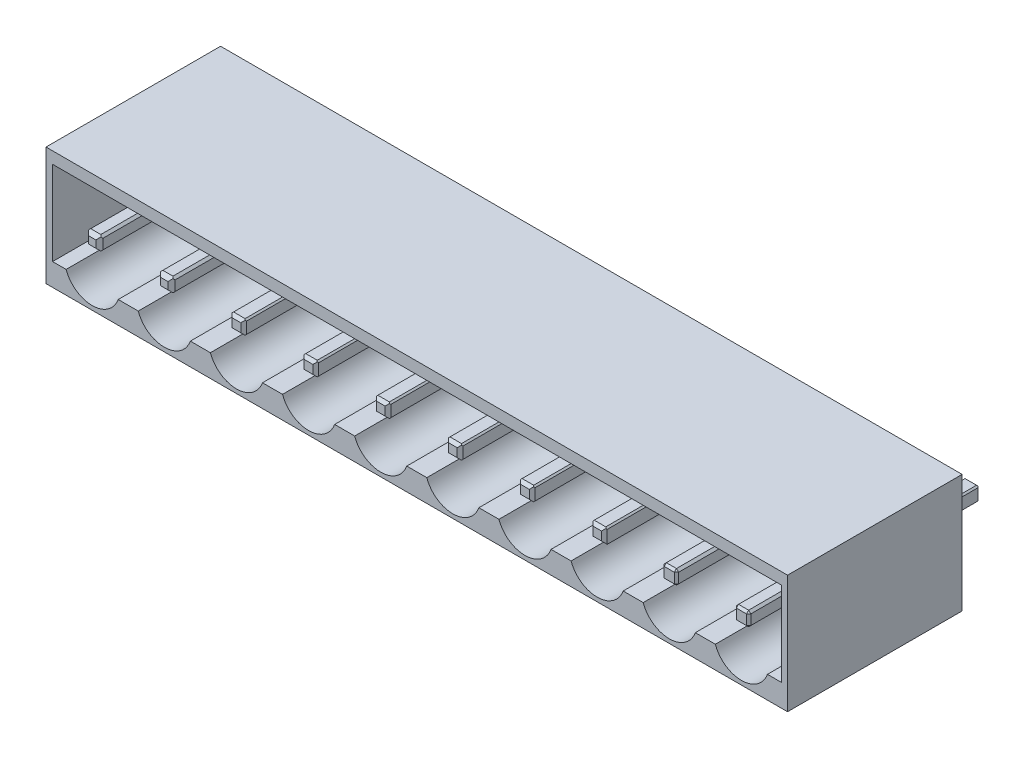
SolidWorks part; units mm, degrees
ref_plane "Спереди" through (0, 0, 0) normal (0, 0, 1) x (1, 0, 0)
ref_plane "Сверху" through (0, 0, 0) normal (0, 1, 0) x (1, 0, 0)
ref_plane "Справа" through (0, 0, 0) normal (1, 0, 0) x (0, 0, -1)
sketch "Эскиз1" plane through (0, 0, 0) normal (0, 0, 1) x (1, 0, 0)
  line L1 (-25.7, 4.1) -> (25.7, 4.1)
  line L2 (-25.7, 4.1) -> (-25.7, -4.1)
  line L3 (-25.7, -4.1) -> (25.7, -4.1)
  line L4 (25.7, 4.1) -> (25.7, -4.1)
  line L5 (-25.7, 4.1) -> (25.7, -4.1) construction
  line L6 (-25.7, -4.1) -> (25.7, 4.1) construction
  point P0 (0, 0)
  dimension "D1" = 8.2
  dimension "D2" = 51.4
extrude "Бобышка-Вытянуть1" add sketch "Эскиз1" along normal blind 12.1
sketch "Эскиз4" plane through (0, 0, 12.1) normal (0, 0, 1) x (1, 0, 0)
  circle A0 centre (-22.5, 0) radius 1.25
  circle A1 centre (-17.5, 0) radius 1.25
  circle A2 centre (-12.5, 0) radius 1.25
  circle A3 centre (-7.5, 0) radius 1.25
  circle A4 centre (-2.5, 0) radius 1.25
  circle A5 centre (2.5, 0) radius 1.25
  circle A6 centre (7.5, 0) radius 1.25
  circle A7 centre (12.5, 0) radius 1.25
  circle A8 centre (17.5, 0) radius 1.25
  circle A9 centre (22.5, 0) radius 1.25
  dimension "D1" = 2.5
  dimension "D2" = 3.2
  dimension "D5" = 2
  dimension "D3" = 2
  dimension "D4" = 2
  dimension "D6" = 3
  dimension "D7" = 2
  dimension "D8" = 2
extrude "Вырез-Вытянуть3" cut sketch "Эскиз4" against normal blind 8
sketch "Эскиз5" plane through (0, 0, 12.1) normal (0, 0, 1) x (1, 0, 0)
  line L0 (-25.2456, 0) -> (-25.2456, 3.2929)
  line L1 (-25.2456, 3.2929) -> (-14.7215, 3.2929)
  line L4 (-25.2456, -2.549) -> (-25.2456, 0)
  line L5 (-15.6942, -2.549) -> (-14.3058, -2.549)
  line L6 (-24.3058, -2.549) -> (-25.2456, -2.549)
  line L7 (-20.6942, -2.549) -> (-19.3058, -2.549)
  line L11 (-14.7215, 3.2929) -> (-9.7215, 3.2929)
  line L13 (-15.6942, -2.549) -> (-14.3058, -2.549) [skipped]
  line L15 (-10.6942, -2.549) -> (-9.3058, -2.549)
  line L16 (-9.7215, 3.2929) -> (-4.7215, 3.2929)
  line L17 (-0.6942, -2.549) -> (0.6942, -2.549)
  line L20 (-5.6942, -2.549) -> (-4.3058, -2.549)
  line L21 (-4.7215, 3.2929) -> (5.2785, 3.2929)
  line L22 (9.3058, -2.549) -> (10.6942, -2.549)
  line L25 (5.2785, 3.2929) -> (15.2785, 3.2929)
  line L26 (4.3058, -2.549) -> (5.6942, -2.549)
  line L27 (19.3058, -2.549) -> (20.6942, -2.549)
  line L28 (24.3058, -2.549) -> (25.2785, -2.549)
  line L29 (25.2785, 3.2929) -> (25.2785, -2.549)
  line L30 (15.2785, 3.2929) -> (25.2785, 3.2929)
  line L31 (14.3058, -2.549) -> (15.6942, -2.549)
  arc A1 (-14.3058, -2.549) -> (-10.6942, -2.549) centre (-12.5, -1.9) ccw
  arc A2 (-9.3058, -2.549) -> (-5.6942, -2.549) centre (-7.5, -1.9) ccw
  arc A4 (-4.3058, -2.549) -> (-0.6942, -2.549) centre (-2.5, -1.9) ccw
  arc A5 (-24.3058, -2.549) -> (-20.6942, -2.549) centre (-22.5, -1.9) ccw
  arc A6 (-19.3058, -2.549) -> (-15.6942, -2.549) centre (-17.5, -1.9) ccw
  arc A7 (0.6942, -2.549) -> (4.3058, -2.549) centre (2.5, -1.9) ccw
  arc A8 (5.6942, -2.549) -> (9.3058, -2.549) centre (7.5, -1.9) ccw
  arc A9 (10.6942, -2.549) -> (14.3058, -2.549) centre (12.5, -1.9) ccw
  arc A10 (15.6942, -2.549) -> (19.3058, -2.549) centre (17.5, -1.9) ccw
  arc A11 (20.6942, -2.549) -> (24.3058, -2.549) centre (22.5, -1.9) ccw
  dimension "D1" = 3.2
  dimension "D2" = 2.2
  dimension "D3" = 2
  dimension "D4" = 2
  dimension "D5" = 2
  dimension "D6" = 2
  dimension "D7" = 2
  dimension "D8" = 2
extrude "Вырез-Вытянуть4" cut sketch "Эскиз5" against normal blind 7.8
sketch "Эскиз7" plane through (0, 0, 4.1) normal (0, 0, 1) x (1, 0, 0)
  line L0 (-18, 0.5) -> (-17, 0.5)
  line L1 (-23, 0.5) -> (-22, 0.5)
  line L2 (-23, 0.5) -> (-23, -0.5)
  line L3 (-23, -0.5) -> (-22, -0.5)
  line L4 (-22, 0.5) -> (-22, -0.5)
  line L5 (-23, 0.5) -> (-22, -0.5) construction
  line L6 (-23, -0.5) -> (-22, 0.5) construction
  line L7 (-18, 0.5) -> (-18, -0.5)
  line L8 (-18, -0.5) -> (-17, -0.5)
  line L9 (-17, 0.5) -> (-17, -0.5)
  line L10 (-18, 0.5) -> (-17, -0.5) construction
  line L11 (-18, -0.5) -> (-17, 0.5) construction
  line L12 (-13, 0.5) -> (-12, 0.5)
  line L13 (-13, 0.5) -> (-13, -0.5)
  line L14 (-13, -0.5) -> (-12, -0.5)
  line L15 (-12, 0.5) -> (-12, -0.5)
  line L16 (-13, 0.5) -> (-12, -0.5) construction
  line L17 (-13, -0.5) -> (-12, 0.5) construction
  line L18 (-8, 0.5) -> (-7, 0.5)
  line L19 (-8, 0.5) -> (-8, -0.5)
  line L20 (-8, -0.5) -> (-7, -0.5)
  line L21 (-7, 0.5) -> (-7, -0.5)
  line L22 (-8, 0.5) -> (-7, -0.5) construction
  line L23 (-8, -0.5) -> (-7, 0.5) construction
  line L24 (-3, 0.5) -> (-2, 0.5)
  line L25 (-3, 0.5) -> (-3, -0.5)
  line L26 (-3, -0.5) -> (-2, -0.5)
  line L27 (-2, 0.5) -> (-2, -0.5)
  line L28 (2, 0.5) -> (3, 0.5)
  line L29 (2, 0.5) -> (2, -0.5)
  line L30 (2, -0.5) -> (3, -0.5)
  line L31 (3, 0.5) -> (3, -0.5)
  line L32 (-3, 0.5) -> (-2, -0.5) construction
  line L33 (-3, -0.5) -> (-2, 0.5) construction
  line L34 (2, 0.5) -> (3, -0.5) construction
  line L35 (2, -0.5) -> (3, 0.5) construction
  line L36 (7, 0.5) -> (8, 0.5)
  line L37 (7, 0.5) -> (7, -0.5)
  line L38 (7, -0.5) -> (8, -0.5)
  line L39 (8, 0.5) -> (8, -0.5)
  line L40 (12, 0.5) -> (13, 0.5)
  line L41 (12, 0.5) -> (12, -0.5)
  line L42 (12, -0.5) -> (13, -0.5)
  line L43 (13, 0.5) -> (13, -0.5)
  line L44 (7, 0.5) -> (8, -0.5) construction
  line L45 (7, -0.5) -> (8, 0.5) construction
  line L46 (12, 0.5) -> (13, -0.5) construction
  line L47 (12, -0.5) -> (13, 0.5) construction
  line L48 (17, 0.5) -> (18, 0.5)
  line L49 (17, 0.5) -> (17, -0.5)
  line L50 (17, -0.5) -> (18, -0.5)
  line L51 (18, 0.5) -> (18, -0.5)
  line L52 (22, 0.5) -> (23, 0.5)
  line L53 (22, 0.5) -> (22, -0.5)
  line L54 (22, -0.5) -> (23, -0.5)
  line L55 (23, 0.5) -> (23, -0.5)
  line L56 (17, 0.5) -> (18, -0.5) construction
  line L57 (17, -0.5) -> (18, 0.5) construction
  line L58 (22, 0.5) -> (23, -0.5) construction
  line L59 (22, -0.5) -> (23, 0.5) construction
  point P0 (-22.5, 0)
  point P7 (-17.5, 0)
  point P12 (-12.5, 0)
  point P17 (-7.5, 0)
  point P23 (-2.5, 0)
  point P28 (2.5, 0)
  point P33 (7.5, 0)
  point P38 (12.5, 0)
  point P43 (17.5, 0)
  point P48 (22.5, 0)
  dimension "D1" = 1
  dimension "D2" = 1
  dimension "D3" = 2
  dimension "D4" = 2
  dimension "D5" = 2
  dimension "D6" = 2
  dimension "D7" = 2
  dimension "D8" = 2
extrude "Бобышка-Вытянуть2" add sketch "Эскиз7" along normal blind 8
chamfer "Фаска1" distance 0.15 angle 45 24 edges at (-18, -0.5, 8.1) (-18, 0.5, 8.1) (-17, 0.5, 8.1) (-17, -0.5, 8.1) (-22, -0.5, 8.1) (-22, 0.5, 8.1) (-23, -0.5, 8.1) (-23, 0.5, 8.1) (23, 0, 12.1) (23, -0.5, 8.1) (22.5, -0.5, 12.1) (22, -0.5, 8.1) (22, 0, 12.1) (22, 0.5, 8.1) (22.5, 0.5, 12.1) (23, 0.5, 8.1) (18, 0, 12.1) (18, -0.5, 8.1) (17.5, -0.5, 12.1) (17, -0.5, 8.1) (17, 0, 12.1) (17, 0.5, 8.1) (17.5, 0.5, 12.1) (18, 0.5, 8.1)
chamfer "Фаска2" distance 0.25 angle 45 8 edges at (-18, 0, 12.1) (-17.5, 0.5, 12.1) (-17, 0, 12.1) (-17.5, -0.5, 12.1) (-22, 0, 12.1) (-22.5, -0.5, 12.1) (-23, 0, 12.1) (-22.5, 0.5, 12.1)
sketch "Эскиз8" plane through (0, -4.1, 0) normal (0, 0, 1) x (-1, 0, 0)
  line L0 (18, -4.25) -> (17, -4.25)
  line L1 (23, -4.25) -> (22, -4.25)
  line L2 (23, -4.25) -> (23, -3.25)
  line L3 (23, -3.25) -> (22, -3.25)
  line L4 (22, -4.25) -> (22, -3.25)
  line L5 (23, -4.25) -> (22, -3.25) construction
  line L6 (23, -3.25) -> (22, -4.25) construction
  line L7 (18, -4.25) -> (18, -3.25)
  line L8 (18, -3.25) -> (17, -3.25)
  line L9 (17, -4.25) -> (17, -3.25)
  line L10 (18, -4.25) -> (17, -3.25) construction
  line L11 (18, -3.25) -> (17, -4.25) construction
  line L12 (13, -4.25) -> (12, -4.25)
  line L13 (13, -4.25) -> (13, -3.25)
  line L14 (13, -3.25) -> (12, -3.25)
  line L15 (12, -4.25) -> (12, -3.25)
  line L16 (13, -4.25) -> (12, -3.25) construction
  line L17 (13, -3.25) -> (12, -4.25) construction
  line L18 (8, -4.25) -> (7, -4.25)
  line L19 (8, -4.25) -> (8, -3.25)
  line L20 (8, -3.25) -> (7, -3.25)
  line L21 (7, -4.25) -> (7, -3.25)
  line L22 (8, -4.25) -> (7, -3.25) construction
  line L23 (8, -3.25) -> (7, -4.25) construction
  line L24 (3, -4.25) -> (2, -4.25)
  line L25 (3, -4.25) -> (3, -3.25)
  line L26 (3, -3.25) -> (2, -3.25)
  line L27 (2, -4.25) -> (2, -3.25)
  line L28 (-2, -4.25) -> (-3, -4.25)
  line L29 (-2, -4.25) -> (-2, -3.25)
  line L30 (-2, -3.25) -> (-3, -3.25)
  line L31 (-3, -4.25) -> (-3, -3.25)
  line L32 (3, -4.25) -> (2, -3.25) construction
  line L33 (3, -3.25) -> (2, -4.25) construction
  line L34 (-2, -4.25) -> (-3, -3.25) construction
  line L35 (-2, -3.25) -> (-3, -4.25) construction
  line L36 (-7, -4.25) -> (-8, -4.25)
  line L37 (-7, -4.25) -> (-7, -3.25)
  line L38 (-7, -3.25) -> (-8, -3.25)
  line L39 (-8, -4.25) -> (-8, -3.25)
  line L40 (-12, -4.25) -> (-13, -4.25)
  line L41 (-12, -4.25) -> (-12, -3.25)
  line L42 (-12, -3.25) -> (-13, -3.25)
  line L43 (-13, -4.25) -> (-13, -3.25)
  line L44 (-7, -4.25) -> (-8, -3.25) construction
  line L45 (-7, -3.25) -> (-8, -4.25) construction
  line L46 (-12, -4.25) -> (-13, -3.25) construction
  line L47 (-12, -3.25) -> (-13, -4.25) construction
  line L48 (-17, -4.25) -> (-18, -4.25)
  line L49 (-17, -4.25) -> (-17, -3.25)
  line L50 (-17, -3.25) -> (-18, -3.25)
  line L51 (-18, -4.25) -> (-18, -3.25)
  line L52 (-22, -4.25) -> (-23, -4.25)
  line L53 (-22, -4.25) -> (-22, -3.25)
  line L54 (-22, -3.25) -> (-23, -3.25)
  line L55 (-23, -4.25) -> (-23, -3.25)
  line L56 (-17, -4.25) -> (-18, -3.25) construction
  line L57 (-17, -3.25) -> (-18, -4.25) construction
  line L58 (-22, -4.25) -> (-23, -3.25) construction
  line L59 (-22, -3.25) -> (-23, -4.25) construction
  point P0 (22.5, -3.75)
  point P7 (17.5, -3.75)
  point P12 (12.5, -3.75)
  point P18 (7.5, -3.75)
  point P23 (2.5, -3.75)
  point P28 (-2.5, -3.75)
  point P33 (-7.5, -3.75)
  point P38 (-12.5, -3.75)
  point P43 (-17.5, -3.75)
  point P48 (-22.5, -3.75)
  dimension "D1" = 1
  dimension "D2" = 1
  dimension "D3" = 3.2
  dimension "D4" = 4.45
  dimension "D5" = 2
  dimension "D6" = 2
  dimension "D7" = 2
  dimension "D8" = 2
  dimension "D9" = 2
  dimension "D10" = 2
extrude "Бобышка-Вытянуть3" add sketch "Эскиз8" against normal blind 4
chamfer "Фаска6" distance 0.1 angle 45 4 edges at (-13, -0.5, 8.1) (-12, -0.5, 8.1) (-12, 0.5, 8.1) (-13, 0.5, 8.1)
chamfer "Фаска7" distance 0.2 angle 45 4 edges at (-12, 0, 12.1) (-12.5, -0.5, 12.1) (-13, 0, 12.1) (-12.5, 0.5, 12.1)
chamfer "Фаска10" distance 0.1 angle 45 12 edges at (-23, -0.85, -2) (-23, 0.15, -2) (-18, -0.85, -2) (-18, 0.15, -2) (-13, -0.85, -2) (-13, 0.15, -2) (-22, -0.85, -2) (-17, -0.85, -2) (-12, -0.85, -2) (-22, 0.15, -2) (-17, 0.15, -2) (-12, 0.15, -2)
chamfer "Фаска11" distance 0.2 angle 45 12 edges at (-22, -0.35, -4) (-22.5, 0.15, -4) (-23, -0.35, -4) (-22.5, -0.85, -4) (-17.5, -0.85, -4) (-18, -0.35, -4) (-17.5, 0.15, -4) (-17, -0.35, -4) (-13, -0.35, -4) (-12.5, 0.15, -4) (-12, -0.35, -4) (-12.5, -0.85, -4)
chamfer "Фаска12" distance 0.1 angle 45 20 edges at (-8, 0.15, -2) (-8, -0.85, -2) (-7, 0.15, -2) (-7, -0.85, -2) (2, -0.5, 8.1) (-3, -0.5, 8.1) (-3, 0.5, 8.1) (-2, 0.5, 8.1) (-2, -0.5, 8.1) (3, -0.5, 8.1) (2, 0.5, 8.1) (3, 0.5, 8.1) (2, -0.85, -2) (2, 0.15, -2) (3, -0.85, -2) (3, 0.15, -2) (-2, -0.85, -2) (-2, 0.15, -2) (-3, -0.85, -2) (-3, 0.15, -2)
chamfer "Фаска13" distance 0.2 angle 45 4 edges at (-7.5, 0.15, -4) (-7, -0.35, -4) (-8, -0.35, -4) (-7.5, -0.85, -4)
chamfer "Фаска14" distance 0.1 angle 45 26 edges at (-7, 0.5, 8.1) (-7, -0.5, 8.1) (-8, -0.5, 8.1) (-8, 0.5, 8.1) (7, -0.5, 8.1) (8, -0.5, 8.1) (13, 0.5, 8.1) (12, 0.5, 8.1) (7, 0.5, 8.1) (8, 0.5, 8.1) (8, -0.85, -2) (13, -0.85, -2) (13, 0.15, -2) (12, 0.15, -2) (12, -0.85, -2) (7, -0.85, -2) (8, 0.15, -2) (7, 0.15, -2) (23, -0.85, -2) (23, 0.15, -2) (22, -0.85, -2) (22, 0.15, -2) (17, 0.15, -2) (17, -0.85, -2) (18, -0.85, -2) (18, 0.15, -2)
chamfer "Фаска15" distance 0.2 angle 45 44 edges at (-8, 0, 12.1) (-7.5, -0.5, 12.1) (-7, 0, 12.1) (-7.5, 0.5, 12.1) (-3, -0.35, -4) (-2.5, -0.85, -4) (-2, -0.35, -4) (-2.5, 0.15, -4) (2, -0.35, -4) (2.5, -0.85, -4) (3, -0.35, -4) (2.5, 0.15, -4) (3, 0, 12.1) (2.5, -0.5, 12.1) (2, 0, 12.1) (2.5, 0.5, 12.1) (-2.5, -0.5, 12.1) (-2, 0, 12.1) (-3, 0, 12.1) (-2.5, 0.5, 12.1) (12.5, -0.85, -4) (13, -0.35, -4) (12, -0.35, -4) (12.5, 0.15, -4) (8, -0.35, -4) (7.5, -0.85, -4) (7, -0.35, -4) (7.5, 0.15, -4) (13, -0.05, 12.1) (12.5, -0.5, 12.1) (12, -0.05, 12.1) (12.5, 0.5, 12.1) (7, 0, 12.1) (7.5, -0.5, 12.1) (8, 0, 12.1) (7.5, 0.5, 12.1) (22.5, 0.15, -4) (23, -0.35, -4) (22.5, -0.85, -4) (22, -0.35, -4) (17, -0.35, -4) (17.5, -0.85, -4) (18, -0.35, -4) (17.5, 0.15, -4)
